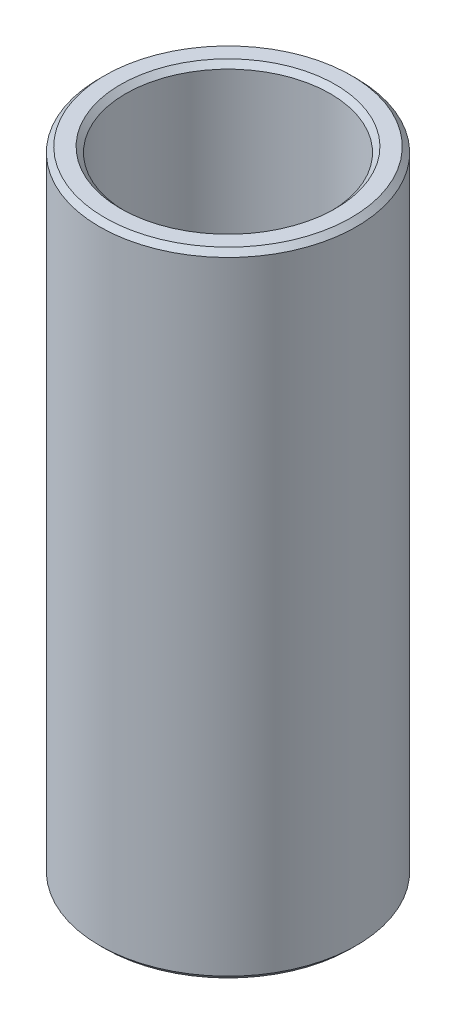
SolidWorks part; units mm, degrees
ref_plane "Front Plane" through (0, 0, 0) normal (0, 0, 1) x (1, 0, 0)
ref_plane "Top Plane" through (0, 0, 0) normal (0, 1, 0) x (1, 0, 0)
ref_plane "Right Plane" through (0, 0, 0) normal (1, 0, 0) x (0, 0, -1)
sketch "Sketch1" plane through (0, 0, 0) normal (0, 1, 0) x (1, 0, 0)
  circle A0 centre (0, 0) radius 22.5
  dimension "SLEEVE_OD" = 45
extrude "Boss-Extrude1" add sketch "Sketch1" along normal blind 110.8489
sketch "Sketch2" plane through (0, 0, 0) normal (0, 1, 0) x (1, 0, 0)
  circle A0 centre (0, 0) radius 17.9031
  dimension "BORE_D" = 35.8062
extrude "Cut-Extrude1" cut sketch "Sketch2" along normal through all
chamfer "Chamfer1" distance 0.9169 angle 45 4 edges at (0, 110.8489, 17.9031) (0, 0, 17.9031) (0, 0, 22.5) (0, 110.8489, 22.5)
